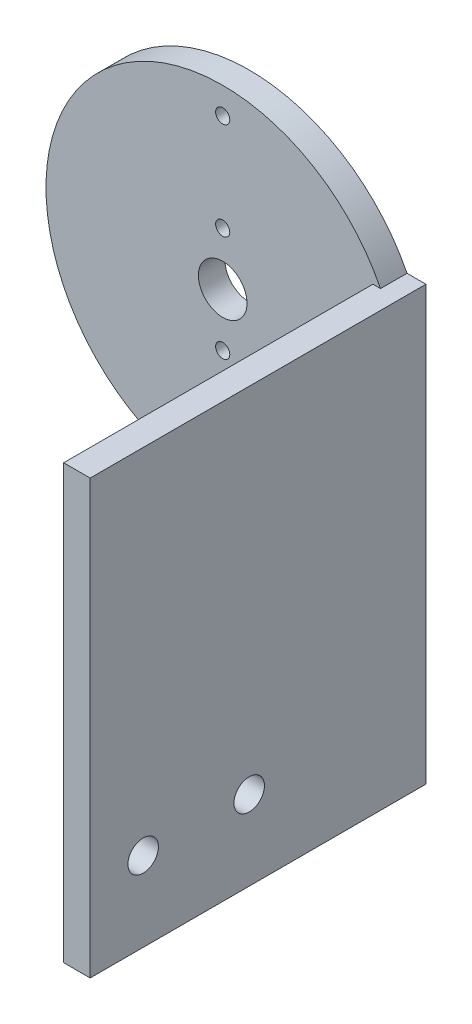
SolidWorks part; units mm, degrees
ref_plane "Front Plane" through (0, 0, 0) normal (0, 0, 1) x (1, 0, 0)
ref_plane "Top Plane" through (0, 0, 0) normal (0, 1, 0) x (1, 0, 0)
ref_plane "Right Plane" through (0, 0, 0) normal (1, 0, 0) x (0, 0, -1)
sketch "Sketch1" plane through (0, 0, 0) normal (0, 0, 1) x (1, 0, 0)
  circle A0 centre (0, 0) radius 20
extrude "Boss-Extrude1" add sketch "Sketch1" along normal blind 3 from offset 26 offset against normal yes
sketch "Sketch2" plane through (0, 0, 0) normal (0, 0, 1) x (1, 0, 0)
  line L0 (0, -40) -> (20, -40)
  line L1 (20, -40) -> (20, 9)
  line L2 (20, 9) -> (0, 9)
  line L3 (0, 9) -> (0, -40)
extrude "Boss-Extrude2" add sketch "Sketch2" along normal blind 3 from offset 26 offset against normal yes
sketch "Sketch3" plane through (0, 0, 0) normal (0, 0, 1) x (1, 0, 0)
  line L0 (17, -40) -> (20, -40)
  line L1 (20, -40) -> (20, 9)
  line L2 (20, 9) -> (17, 9)
  line L3 (17, 9) -> (17, -40)
extrude "Boss-Extrude3" add sketch "Sketch3" along normal blind 38 from offset 26 offset against normal yes
sketch "Sketch4" plane through (0, 0, 0) normal (0, 0, 1) x (1, 0, 0)
  circle A0 centre (0, 0) radius 2.75
  circle A1 centre (0, 6) radius 0.8
  circle A2 centre (0, -6) radius 0.8
  circle A3 centre (0, 17) radius 0.8
  circle A4 centre (0, -17) radius 0.8
extrude "Cut-Extrude1" cut sketch "Sketch4" against normal through all and the other way through all
sketch "Sketch5" plane through (0, 0, 0) normal (1, 0, 0) x (0, 0, -1)
  circle A0 centre (-6, -31) radius 1.725
  circle A1 centre (6, -31) radius 1.725
extrude "Cut-Extrude2" cut sketch "Sketch5" against normal through all and the other way through all
